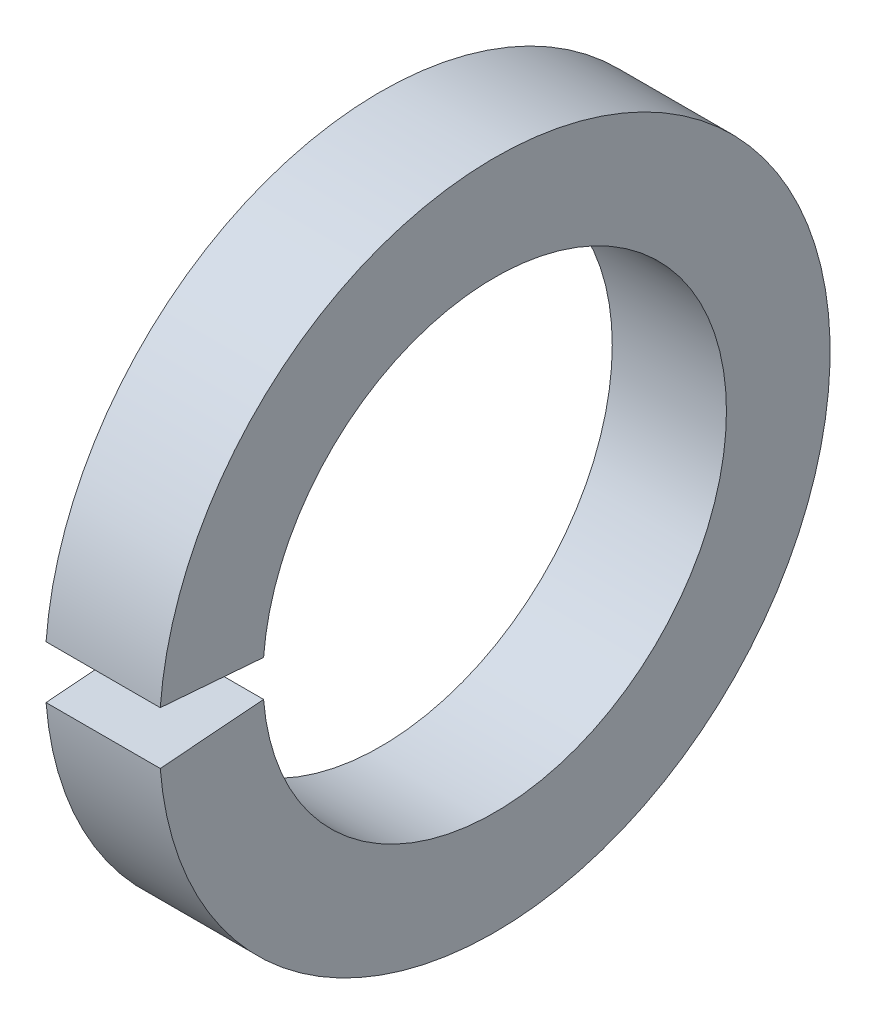
SolidWorks part; units mm, degrees
ref_plane "Plane1" through (0, 0, 0) normal (0, 0, 1) x (1, 0, 0)
ref_plane "Plane2" through (0, 0, 0) normal (0, 1, 0) x (1, 0, 0)
ref_plane "Plane3" through (0, 0, 0) normal (1, 0, 0) x (0, 0, -1)
sketch "Sketch1" plane through (0, 0, 0) normal (0, 0, 1) x (1, 0, 0)
  line L0 (-34.925, 0) -> (9.525, 0) construction
  line L1 (0, 12.8905) -> (0, 18.6563)
  line L2 (0, 18.6563) -> (-6.35, 18.6563)
  line L3 (-6.35, 18.6563) -> (-6.35, 12.8905)
  line L4 (-6.35, 12.8905) -> (0, 12.8905)
  dimension "Thickness" = 6.35
revolve "Base-Revolve" add sketch "Sketch1" angle 360 about L0
sketch "Sketch2" plane through (0, 0, 0) normal (-1, 0, 0) x (0, -1, 0)
  line L0 (0, 0) -> (1.493, 18.9708)
  line L1 (0, -3.175) -> (0, 12.7) construction
  line L2 (0, 0) -> (-1.493, 18.9708)
  arc A0 (1.493, 18.9708) -> (-1.493, 18.9708) centre (0, 0) ccw
  dimension "D1" = 19.0294
extrude "Gap" cut sketch "Sketch2" along normal through all
equation "\"D1@Sketch2\" = \"Outside_dia@Sketch1\" * 0.51"
